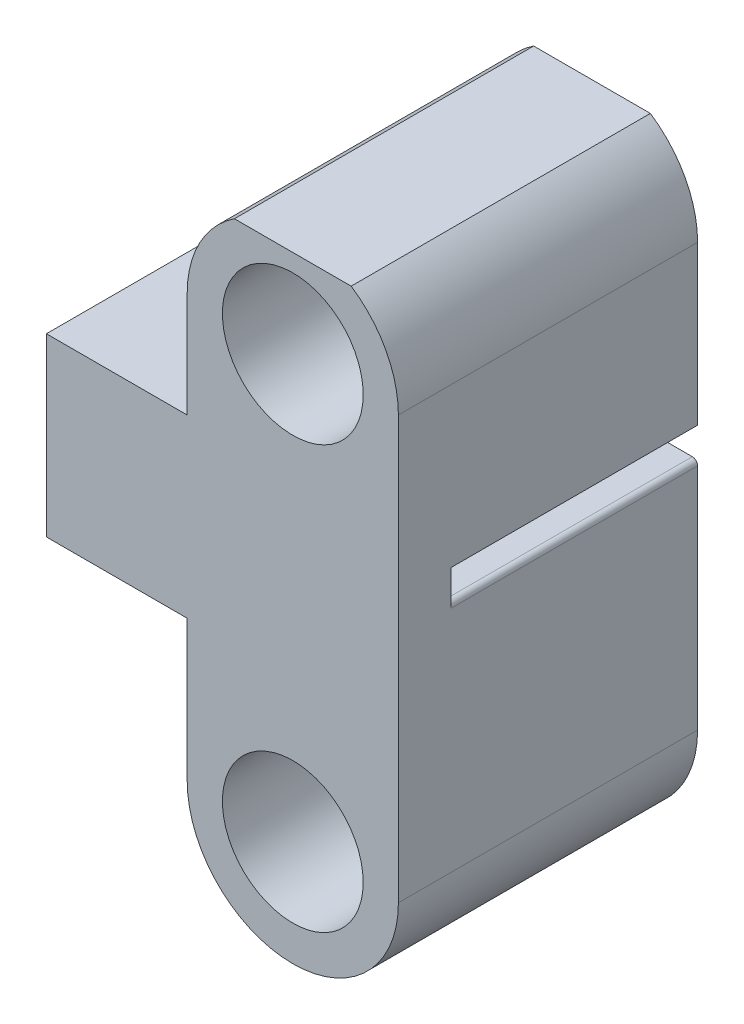
SolidWorks part; units mm, degrees
ref_plane "Front Plane" through (0, 0, 0) normal (0, 0, 1) x (1, 0, 0)
ref_plane "Top Plane" through (0, 0, 0) normal (0, 1, 0) x (1, 0, 0)
ref_plane "Right Plane" through (0, 0, 0) normal (1, 0, 0) x (0, 0, -1)
sketch "Sketch1" plane through (0, 0, 0) normal (0, 0, 1) x (1, 0, 0)
  line L0 (0, 0) -> (0, -12) construction
  line L1 (-3, 0) -> (-3, -12)
  line L2 (3, 0) -> (3, -12)
  arc A0 (3, 0) -> (-3, 0) centre (0, 0) ccw
  arc A1 (-3, -12) -> (3, -12) centre (0, -12) ccw
  circle A2 centre (0, 0) radius 2
  circle A3 centre (0, -12) radius 2
  dimension "D2" = 6
  dimension "D6" = 4
  dimension "D7" = 4
  dimension "D1" = 12
extrude "Boss-Extrude1" add sketch "Sketch1" along normal blind 8.5
sketch "Sketch2" plane through (3, 0, 0) normal (1, 0, 0) x (0, 0, -1)
  line L0 (-8.5, -6) -> (0, -6) construction
  line L1 (-8.5, -12) -> (-8.5, 0) construction
  line L2 (0, -12) -> (0, 0) construction
  line L3 (-4.25, 0) -> (-4.25, -12) construction
  line L4 (-8.5, 0) -> (0, 0) construction
  line L5 (-8.5, -12) -> (0, -12) construction
  circle A0 centre (-4.25, -8.5) radius 2
  dimension "D1" = 4
  dimension "D2" = 2.5
extrude "Cut-Extrude1" [suppressed] cut sketch "Sketch2" against normal through all
sketch "Sketch3" [suppressed] plane through (3, 0, 0) normal (1, 0, 0) x (0, 0, -1)
  line L1 (-0.6416, -8.5) -> (-2.4458, -5.375)
  line L2 (-2.4458, -5.375) -> (-6.0542, -5.375)
  line L3 (-6.0542, -5.375) -> (-7.8584, -8.5)
  line L4 (-7.8584, -8.5) -> (-6.0542, -11.625)
  line L5 (-6.0542, -11.625) -> (-2.4458, -11.625)
  line L6 (-2.4458, -11.625) -> (-0.6416, -8.5)
  line L7 (-1.8684, -4.375) -> (-6.6316, -4.375)
  line L8 (-6.6316, -4.375) -> (-9.0131, -8.5)
  line L9 (-9.0131, -8.5) -> (-6.6316, -12.625)
  line L10 (-6.6316, -12.625) -> (-1.8684, -12.625)
  line L11 (-1.8684, -12.625) -> (0.5131, -8.5)
  line L12 (0.5131, -8.5) -> (-1.8684, -4.375)
  circle A0 centre (-4.25, -8.5) radius 3.125 construction
  circle A1 centre (-4.25, -8.5) radius 4.125 construction
  dimension "D1" = 6.25
  dimension "D2" = 1
extrude "Boss-Extrude2" [suppressed] add sketch "Sketch3" along normal blind 2 and the other way blind 0.5
sketch "Sketch4" [suppressed] plane through (-3, 0, 0) normal (-1, 0, 0) x (0, 0, 1)
  line L0 (4.25, 0) -> (4.25, -6.5) construction
  line L1 (8.5, 0) -> (0, 0) construction
  line L3 (0.75, -2.75) -> (7.75, -2.75)
  line L4 (0.75, -2.75) -> (0.75, -5.75)
  line L5 (0.75, -5.75) -> (7.75, -5.75)
  line L6 (7.75, -2.75) -> (7.75, -5.75)
  line L7 (0.75, -2.75) -> (7.75, -5.75) construction
  line L8 (0.75, -5.75) -> (7.75, -2.75) construction
  circle A0 centre (4.25, -8.5) radius 2 construction
  point P7 (4.25, -4.25)
  dimension "D1" = 7
  dimension "D2" = 3
  dimension "D3" = 2.75
extrude "Cut-Extrude2" [suppressed] cut sketch "Sketch4" against normal through all
sketch "Sketch5" plane through (-3, 0, 0) normal (-1, 0, 0) x (0, 0, 1)
  line L0 (4.25, 0) -> (4.25, -12) construction
  line L1 (8.5, 0) -> (0, 0) construction
  line L2 (8.5, -12) -> (0, -12) construction
  line L3 (0, -6) -> (8.5, -6) construction
  line L4 (0, 0) -> (0, -12) construction
  line L5 (8.5, 0) -> (8.5, -12) construction
  line L7 (0, -15) -> (8.5, -15)
  line L8 (0, -15) -> (0, 3)
  line L9 (0, 3) -> (8.5, 3)
  line L10 (8.5, -15) -> (8.5, 3)
  line L11 (0, -15) -> (8.5, 3) construction
  line L12 (0, 3) -> (8.5, -15) construction
  point P12 (4.25, -6)
extrude "Cut-Extrude3" [suppressed] cut sketch "Sketch5" against normal through all flip side to cut
sketch "Sketch9" plane through (-3, 0, 0) normal (-1, 0, 0) x (0, 0, 1)
  line L0 (8.5, 0) -> (8.5, -12) construction
  line L1 (0, -3) -> (8.5, -3)
  line L2 (0, -3) -> (0, -8)
  line L3 (0, -8) -> (8.5, -8)
  line L4 (8.5, -3) -> (8.5, -8)
  line L5 (0, 0) -> (0, -12) construction
  line L6 (8.5, 0) -> (0, 0) construction
  dimension "D1" = 5
  dimension "D2" = 3
extrude "Boss-Extrude4" add sketch "Sketch9" along normal blind 4
sketch "Sketch6" plane through (3, 0, 0) normal (1, 0, 0) x (0, 0, -1)
  line L0 (0, -12) -> (0, 0) construction
  line L1 (0, -4.5) -> (-7, -4.5)
  line L2 (0, -4.5) -> (0, -6.1)
  line L3 (0, -6.1) -> (-7, -6.1)
  line L4 (-7, -4.5) -> (-7, -6.1)
  dimension "D1" = 1.6
  dimension "D2" = 4.5
  dimension "D3" = 7
extrude "Cut-Extrude5" cut sketch "Sketch6" against normal through all
sketch "Sketch7" plane through (0, 0, 7) normal (0, 0, -1) x (-1, 0, 0)
  line L0 (-3, -6.1) -> (-3, -5.5)
  line L1 (-3, -4.5) -> (-3, -6.1) construction
  line L2 (-2.85, -5.35) -> (-2.15, -5.35)
  line L3 (-2, -5.5) -> (-2, -6.1)
  line L4 (7, -6.1) -> (-3, -6.1) construction
  line L5 (-2, -6.1) -> (-3, -6.1)
  line L6 (-0.85, -5.35) -> (-0.15, -5.35)
  line L7 (0, -5.5) -> (0, -6.1)
  line L8 (0, -6.1) -> (-1, -6.1)
  line L9 (-1, -6.1) -> (-1, -5.5)
  line L10 (1.15, -5.35) -> (1.85, -5.35)
  line L11 (2, -5.5) -> (2, -6.1)
  line L12 (2, -6.1) -> (1, -6.1)
  line L13 (1, -6.1) -> (1, -5.5)
  line L14 (3.15, -5.35) -> (3.85, -5.35)
  line L15 (4, -5.5) -> (4, -6.1)
  line L16 (4, -6.1) -> (3, -6.1)
  line L17 (3, -6.1) -> (3, -5.5)
  line L18 (5.15, -5.35) -> (5.85, -5.35)
  line L19 (6, -5.5) -> (6, -6.1)
  line L20 (6, -6.1) -> (5, -6.1)
  line L21 (5, -6.1) -> (5, -5.5)
  arc A0 (-2.15, -5.35) -> (-2, -5.5) centre (-2.15, -5.5) cw
  arc A1 (-3, -5.5) -> (-2.85, -5.35) centre (-2.85, -5.5) cw
  arc A2 (-1, -5.5) -> (-0.85, -5.35) centre (-0.85, -5.5) cw
  arc A3 (-0.15, -5.35) -> (0, -5.5) centre (-0.15, -5.5) cw
  arc A4 (1, -5.5) -> (1.15, -5.35) centre (1.15, -5.5) cw
  arc A5 (1.85, -5.35) -> (2, -5.5) centre (1.85, -5.5) cw
  arc A6 (3, -5.5) -> (3.15, -5.35) centre (3.15, -5.5) cw
  arc A7 (3.85, -5.35) -> (4, -5.5) centre (3.85, -5.5) cw
  arc A8 (5, -5.5) -> (5.15, -5.35) centre (5.15, -5.5) cw
  arc A9 (5.85, -5.35) -> (6, -5.5) centre (5.85, -5.5) cw
  point P11 (-2, -5.35)
  point P14 (-3, -5.35)
  dimension "D3" = 0.15
  dimension "D1" = 1
  dimension "D2" = 0.75
  dimension "D4" = 5
extrude "Boss-Extrude3" add sketch "Sketch7" along normal through all
sketch "Sketch10" plane through (0, 0, 8.5) normal (0, 0, 1) x (1, 0, 0)
  line L1 (-2.5, 3.5) -> (2.5, 3.5)
  line L2 (-2.5, 3.5) -> (-2.5, 2.5)
  line L3 (-2.5, 2.5) -> (2.5, 2.5)
  line L4 (2.5, 3.5) -> (2.5, 2.5)
  line L5 (-2.5, 3.5) -> (2.5, 2.5) construction
  line L6 (-2.5, 2.5) -> (2.5, 3.5) construction
  arc A0 (3, 0) -> (-3, 0) centre (0, 0) ccw construction
  point P0 (0, 3)
  dimension "D1" = 1
  dimension "D2" = 5
extrude "Cut-Extrude6" cut sketch "Sketch10" against normal through all
equation "\"X-ROD-SPACING\"=45"
equation "\"Y-ROD-SPACING\"=75"
equation "\"Z-ROD-SPACING\"=17.5"
equation "\"Y-BED-OFFSET\"=2"
equation "\"Y-BED-ROD-INSET\"=3.5"
equation "\"Y-BED-SCREW-SPACING\"=209"
equation "\"Y-BED-SCREW-CUTOUT-SLOT-HEIGHT\"=2.5"
equation "\"T-SLOT-NUT-FILLET-RADIUS\"=0.5"
equation "\"T-SLOT-SCREW-SHAFT-RADIUS\"=1.55"
equation "\"T-SLOT-SCREW-SHAFT-CUTOUT-LENGTH\"=11"
equation "\"T-SLOT-NUT-DEPTH\"=3.5"
equation "\"T-SLOT-NUT-WIDTH\"=2.85"
equation "\"T-SLOT-NUT-END-DISTANCE\"=8"
equation "\"ACRYLIC-THICKNESS\"=10"
equation "\"ACRYLIC-THICKNESS2\"=4.5"
equation "\"ACRYLIC-TAB-CUTOUT-SIZE\"=\"ACRYLIC-THICKNESS\"+\"ACRYLIC-TAB-TOLERANCE\"*2"
equation "\"ACRYLIC-TAB-TOLERANCE\"=-.05"
equation "\"ACRYLIC-TAB-WIDTH\"=\"ACRYLIC-THICKNESS\""
equation "\"ACRYLIC-M3-HOLE\"=2.9"
equation "\"SMOOTHROD-CAP-SCREW-DISTANCE\"=20"
equation "\"FRAME-WIDTH-INNER\"=370"
equation "\"NEMA17-HOLE-SPACING\"=31"
equation "\"NEMA17-CENTRAL-CUTOUT\"=22.5"
equation "\"Z-BRACKET-REACH\"=57"
equation "\"Z-ROD-INSET\"=13.5"
equation "\"TOP-BRACKET-SPACING\"=40"
equation "\"SMOOTHROD-X-LENGTH\"=350"
equation "\"SMOOTHROD-Y-LENGTH\"=350"
equation "\"SMOOTHROD-Z-LENGTH\"=350"
equation "\"SMOOTHROD-TIGHTENING-HEADROOM\"=.25"
equation "\"LEADSCREW-Z-LENGTH\"=300"
equation "\"SCREW-LENGTH-FRAME\"=\"ACRYLIC-THICKNESS\" + 10"
equation "\"SCREW-LENGTH-MOTOR\"=\"ACRYLIC-THICKNESS\" + 5"
equation "\"SCREW-LENGTH-EXTRUDER\"=28"
equation "\"SCREW-HEAD-RADIUS\"=6"
equation "\"PRINTED-M3-HOLE\"=3.5"
equation "\"PRINTED-X-SMOOTHROD-DIAMETER\"=8.8"
equation "\"PRINTED-X-SMOOTHROD-CUTOUT\"=10"
equation "\"PRINTED-X-BASE-HEIGHT\"=10"
equation "\"PRINTED-LM8UU-CUTOUT-SIZE\"=15.5"
equation "\"PRINTED-LM8UU-CUTOUT-LENGTH\"=24.5"
equation "\"PRINTED-X-IDLER-HEIGHT\"=16"
equation "\"PRINTED-M3-NUT-AF\"=6.25"
equation "\"PSU-MOUNTING-WIDTH\"=50"
equation "\"PSU-MOUNTING-HEIGHT\"=150"
equation "\"Y-BELT-TO-ROD-DISTANCE\"=20"
equation "\"SPOOL-HOLDER-ROD-SPACING\"=150"
equation "\"ACRYLIC-X-CARRIAGE-WIDTH\"=55"
equation "\"ACRYLIC-X-CARRIAGE-HEIGHT\"=75"
equation "\"ACRYLIC-X-CARRIAGE-LM8UU-CUTOUT-WIDTH\"=24.25"
equation "\"ACRYLIC-X-CARRIAGE-LM8UU-CUTOUT-HEIGHT\"=11.0"
equation "\"ACRYLIC-X-CARRIAGE-SCREW-SPACING-X\"=15"
equation "\"ACRYLIC-X-CARRIAGE-SCREW-SPACING-Y\"=33"
equation "\"ACRYLIC-X-CARRIAGE-CENTER-TAB-SPACING\"=14"
equation "\"ACRYLIC-X-CARRIAGE-EXTRUDER-OFFSET\"=26"
equation "\"ACRYLIC-X-CARRIAGE-EXTRUDER-ANGLE\"=90"
equation "\"ACRYLIC-X-CARRIAGE-EXTRUDER-SHELF-DEPTH\"=\"ACRYLIC-X-CARRIAGE-EXTRUDER-OFFSET\" + 28"
equation "\"ACRYLIC-X-CARRIAGE-EXTRUDER-BRACE-SPACING\"=23"
equation "\"ACRYLIC-X-CARRIAGE-EXTRUDER-BRACE-TAB-OFFSET\"=20"
equation "\"ACRYLIC-X-CARRIAGE-EXTRUDER-BRACE-HEIGHT\"=35"
equation "\"ACRYLIC-X-CARRIAGE-EXTRUDER-BRACE-SCREW-SPACING\"=22"
equation "\"ACRYLIC-X-CARRIAGE-DUAL-WIDTH-MULTIPLIER\"=1.65"
equation "\"ACRYLIC-X-CARRIAGE-DUAL-HOTEND-SPACING\"=42"
equation "\"ACRYLIC-X-CARRIAGE-DUAL-WIDTH\"=75"
equation "\"ACRYLIC-X-CARRIAGE-DUAL-HOTEND-SEPARATION\"=36"
equation "\"ACRYLIC-X-CARRIAGE-DUAL-MOUNT-PLATE-DEPTH\"=75"
equation "\"ACRYLIC-X-CARRIAGE-DUAL-MOUNT-BRACE-WIDTH\"=33"
equation "\"ACRYLIC-X-CARRIAGE-DUAL-MOUNT-SCREW-WIDTH\"=40"
equation "\"BLOWER-FAN-WIDTH\"=15"
equation "\"D1@Sketch3\"=\"PRINTED-M3-NUT-AF\""
